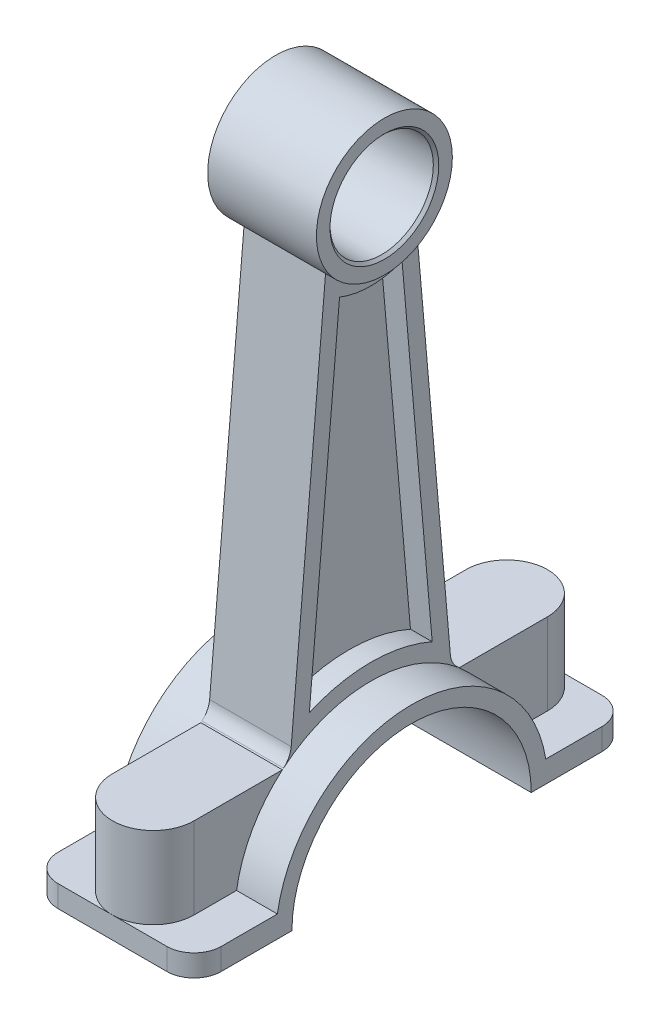
SolidWorks part; units mm, degrees
material "Alloy Steel"
ref_plane "Front Plane" through (0, 0, 0) normal (0, 0, 1) x (1, 0, 0)
ref_plane "Top Plane" through (0, 0, 0) normal (0, 1, 0) x (1, 0, 0)
ref_plane "Right Plane" through (0, 0, 0) normal (1, 0, 0) x (0, 0, -1)
sketch "Sketch3" plane through (0, 0, 0) normal (1, 0, 0) x (0, 0, -1)
  line L0 (40, 0) -> (-40, 0)
  line L1 (-40, 0) -> (-40, 4)
  line L2 (-40, 4) -> (-24.6779, 4)
  line L3 (0, 0) -> (0, 40.4889) construction
  line L4 (40, 0) -> (40, 4)
  line L5 (40, 4) -> (24.6779, 4)
  arc A0 (24.6779, 4) -> (-24.6779, 4) centre (0, 0) ccw
  point P6 (0, 0)
  dimension "D1" = 50
  dimension "D2" = 80
  dimension "D3" = 4
extrude "Boss-Extrude1" add sketch "Sketch3" along normal mid plane 30
sketch "Sketch4" plane through (0, 0, 0) normal (1, 0, 0) x (0, 0, -1)
  line L0 (0, 0) -> (0, 100) construction
  line L1 (-40, 0) -> (40, 0) construction
  line L2 (7.5, 103.4093) -> (16.5471, 0)
  line L3 (-7.5, 103.4093) -> (-16.5471, 0)
  line L4 (-7.5, 103.4093) -> (7.5, 103.4093)
  line L5 (-16.5471, 0) -> (16.5471, 0)
  line L6 (-16.5471, 0) -> (0, 25) construction
  line L7 (0, 25) -> (16.5471, 0) construction
  arc A0 (24.6779, 4) -> (-24.6779, 4) centre (0, 0) ccw construction
  dimension "D1" = 100
  dimension "D2" = 10
  dimension "D3" = 15
  dimension "D4" = 67
extrude "Boss-Extrude2" add sketch "Sketch4" along normal mid plane 15
sketch "Sketch5" plane through (0, 0, 0) normal (1, 0, 0) x (0, 0, -1)
  line L0 (7.5, 103.4093) -> (-7.5, 103.4093) construction
  circle A0 centre (0, 103.4093) radius 12.5
  dimension "D1" = 25
extrude "Boss-Extrude3" add sketch "Sketch5" along normal mid plane 20
sketch "Sketch6" plane through (0, 4, 0) normal (0, 1, 0) x (1, 0, 0)
  line L0 (0, -32.5) -> (0, 32.5) construction
  line L1 (-7.5, -32.5) -> (-7.5, 32.5)
  line L2 (7.5, -32.5) -> (7.5, 32.5)
  line L3 (15, 40) -> (-15, 40) construction
  line L4 (15, -40) -> (-15, -40) construction
  arc A0 (-7.5, -32.5) -> (7.5, -32.5) centre (0, -32.5) ccw
  arc A1 (7.5, 32.5) -> (-7.5, 32.5) centre (0, 32.5) ccw
  point P3 (0, 0)
  dimension "D1" = 15
extrude "Boss-Extrude4" add sketch "Sketch6" along normal blind 15
sketch "Sketch7" plane through (10, 0, 0) normal (1, 0, 0) x (0, 0, -1)
  circle A2 centre (0, 0) radius 22
  arc A3 (24.6779, 4) -> (-24.6779, 4) centre (0, 0) ccw construction
  circle A6 centre (0, 103.4093) radius 9.5
  circle A7 centre (0, 103.4093) radius 9.5
  dimension "D1" = 3
  dimension "D2" = 3
extrude "Cut-Extrude2" cut sketch "Sketch7" against normal through all and the other way through all
sketch "Sketch13" plane through (7.5, 0, 0) normal (1, 0, 0) x (0, 0, -1)
  line L4 (-5.7479, 89.0144) -> (-11.2941, 25.6211)
  line L5 (11.2941, 25.6211) -> (5.7479, 89.0144)
  line L6 (-5.7479, 89.0144) -> (-11.2941, 25.6211)
  line L7 (11.2941, 25.6211) -> (5.7479, 89.0144)
  arc A4 (-5.7479, 89.0144) -> (5.7479, 89.0144) centre (0, 103.4093) ccw
  arc A5 (11.2941, 25.6211) -> (-11.2941, 25.6211) centre (0, 0) ccw
  arc A6 (-5.7479, 89.0144) -> (5.7479, 89.0144) centre (0, 103.4093) ccw
  arc A7 (11.2941, 25.6211) -> (-11.2941, 25.6211) centre (0, 0) ccw
  dimension "D1" = 3
extrude "Cut-Extrude3" cut sketch "Sketch13" against normal blind 4
mirror "Mirror1" about plane through (0, 0, 0) normal (1, 0, 0) of "Cut-Extrude3"
chamfer "Chamfer1" distance 0.5 angle 45 2 edges at (-10, 103.4093, -9.5) (10, 103.4093, -9.5)
fillet "Fillet1" radius 5 4 edges at (-15, 2, -40) (15, 2, -40) (-15, 2, 40) (15, 2, 40)
fillet "Fillet2" radius 4 2 edges at (0, 20.1607, -14.7833) (0, 20.1607, 14.7833)
